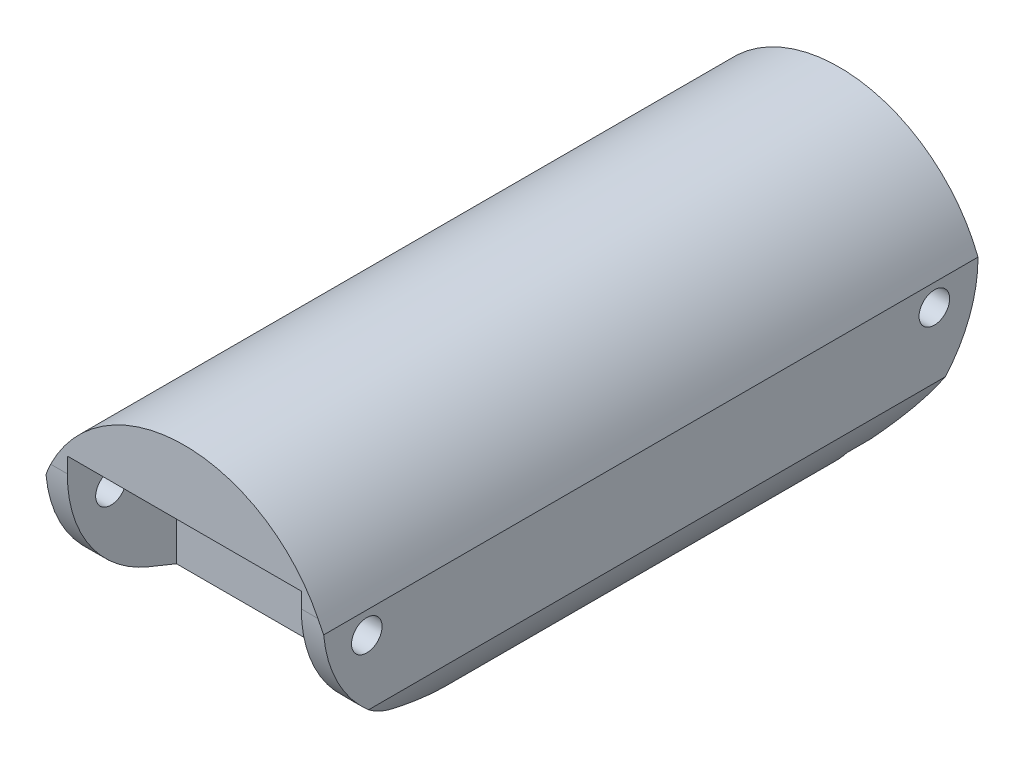
SolidWorks part; units mm, degrees
material "PET"
ref_plane "Front Plane" through (0, 0, 0) normal (0, 0, 1) x (1, 0, 0)
ref_plane "Top Plane" through (0, 0, 0) normal (0, 1, 0) x (1, 0, 0)
ref_plane "Right Plane" through (0, 0, 0) normal (1, 0, 0) x (0, 0, -1)
sketch "Sketch1" plane through (0, 0, 0) normal (0, 0, 1) x (1, 0, 0)
  line L0 (0, 0) -> (0, 5.08)
  line L3 (16.1544, 5.08) -> (16.1544, 0)
  arc A2 (0, 5.08) -> (16.1544, 5.08) centre (8.0772, 1.9574) cw
  arc A3 (0, 0) -> (16.1544, 0) centre (8.0772, 3.1226) ccw
  point P7 (8.0772, -5.5372)
  point P8 (8.0772, 10.6172)
  dimension "D1" = 16.1544
  dimension "D2" = 16.1544
  dimension "D3" = 5.08
extrude "Boss-Extrude1" add sketch "Sketch1" along normal mid plane 38.1 contours A2 L3 A3 L0
sketch "Sketch2" plane through (0, 0, 0) normal (1, 0, 0) x (0, 0, -1)
  line L4 (15.875, 2.54) -> (-49984.125, 2.54) construction
  line L5 (19.05, 5.08) -> (19.05, 0) construction
  line L6 (-19.05, 5.08) -> (-19.05, 0) construction
  line L7 (-19.05, -5.5372) -> (-19.05, 0.635)
  line L8 (-3.81, -5.5372) -> (-19.05, -5.5372)
  line L9 (-19.05, 0.635) -> (-3.81, -5.5372)
  line L10 (0, -1000) -> (0, 49000) construction
  line L18 (19.05, 0.635) -> (19.05, -5.5372)
  line L19 (-16.51, 1.27) -> (-19.05, 1.27)
  line L21 (-16.51, 3.81) -> (-19.05, 3.81)
  line L22 (-19.05, 1.27) -> (-19.05, 3.81)
  line L23 (-15.0884, 2.54) -> (-19.05, 3.81) construction
  line L24 (-15.0884, 2.54) -> (-19.05, 1.27) construction
  line L27 (16.51, 1.27) -> (19.05, 1.27)
  line L28 (19.05, 1.27) -> (19.05, 3.81)
  line L29 (16.51, 3.81) -> (19.05, 3.81)
  line L30 (19.05, -5.5372) -> (8.3594, -5.5372)
  line L31 (-19.05, -5.5372) -> (19.05, -5.5372) construction
  line L32 (8.3594, -5.5372) -> (19.05, 0.635)
  line L33 (-19.05, 10.6172) -> (-19.05, 5.08) construction
  arc A3 (-16.51, 3.81) -> (-16.51, 1.27) centre (-14.3103, 2.54) cw
  arc A4 (16.51, 3.81) -> (16.51, 1.27) centre (14.3103, 2.54) ccw
  point P0 (-15.0884, 2.54)
  point P11 (19.05, 2.54)
  point P14 (-19.05, 2.54)
  point P26 (-19.05, 2.54)
  dimension "D3" = 2.54
  dimension "D4" = 0.635
  dimension "D5" = 60
  dimension "D6" = 0.635
  dimension "D1" = 3.81
extrude "Cut-Extrude1" cut sketch "Sketch2" along normal through all
sketch "Sketch3" plane through (0, 0, 19.05) normal (0, 0, 1) x (1, 0, 0)
  line L3 (-11.7804, 2.54) -> (36.5812, 2.54) construction
  line L4 (8.0772, 9.0576) -> (8.0772, -5.5372) construction
  line L5 (16.1544, 2.54) -> (0, 2.54) construction
  line L6 (16.1544, 2.54) -> (0, 2.54) construction
  line L7 (0, 5.08) -> (0, 0) construction
  line L8 (16.1544, 0.635) -> (0, 0.635) construction
  arc A7 (0, 0) -> (16.1544, 0) centre (8.0772, 3.1226) ccw construction
  arc A9 (14.6124, 0.635) -> (1.542, 0.635) centre (8.0772, 2.54) cw
  arc A13 (5.4577, -3.743) -> (10.6967, -3.743) centre (8.0772, -5.5372) cw
  dimension "D1" = 1.27
  dimension "D2" = 3.175
extrude "Cut-Extrude2" cut sketch "Sketch3" against normal through all contours A13 A9
sketch "Sketch4" plane through (0, 0, 0) normal (-1, 0, 0) x (0, 0, 1)
  line L0 (19.05, 1.27) -> (16.51, 1.27) construction
  line L1 (16.51, 3.81) -> (19.05, 3.81) construction
  line L2 (-16.51, 1.27) -> (-19.05, 1.27) construction
  line L3 (-19.05, 3.81) -> (-16.51, 3.81) construction
  line L4 (19.05, 1.27) -> (16.51, 1.27)
  line L5 (16.51, 3.81) -> (19.05, 3.81)
  line L6 (-16.51, 1.27) -> (-19.05, 1.27)
  line L7 (-19.05, 3.81) -> (-16.51, 3.81)
  line L8 (-19.05, 3.81) -> (-19.05, 1.27)
  line L9 (19.05, 3.81) -> (19.05, 1.27)
  arc A0 (14.3103, 0) -> (16.51, 1.27) centre (14.3103, 2.54) ccw construction
  arc A1 (16.51, 3.81) -> (14.3103, 5.08) centre (14.3103, 2.54) ccw construction
  arc A2 (14.3103, 5.08) -> (14.3103, 0) centre (14.3103, 2.54) ccw construction
  arc A3 (-16.51, 1.27) -> (-14.3103, 0) centre (-14.3103, 2.54) ccw construction
  arc A4 (-14.3103, 5.08) -> (-16.51, 3.81) centre (-14.3103, 2.54) ccw construction
  arc A5 (-14.3103, 0) -> (-14.3103, 5.08) centre (-14.3103, 2.54) ccw construction
  arc A6 (14.3103, 0) -> (16.51, 1.27) centre (14.3103, 2.54) ccw
  arc A7 (16.51, 3.81) -> (14.3103, 5.08) centre (14.3103, 2.54) ccw
  arc A8 (14.3103, 5.08) -> (14.3103, 0) centre (14.3103, 2.54) ccw
  arc A9 (-16.51, 1.27) -> (-14.3103, 0) centre (-14.3103, 2.54) ccw
  arc A10 (-14.3103, 5.08) -> (-16.51, 3.81) centre (-14.3103, 2.54) ccw
  arc A11 (-14.3103, 0) -> (-14.3103, 5.08) centre (-14.3103, 2.54) ccw
extrude "Boss-Extrude2" add sketch "Sketch4" against normal up to surface (16.1544 mm away) up to face at (16.1544, 2.54, 0)
ref_plane "Plane1" through (5.08, 0, 0) normal (-1, 0, 0) x (0, 0, 1)
ref_plane "Plane2" through (8.0772, 0, 0) normal (1, 0, 0) x (0, 0, -1)
sketch "Sketch7" plane through (5.08, 0, 0) normal (-1, 0, 0) x (0, 0, 1)
  line L0 (-19.05, 0) -> (-19.05, 2.8575)
  line L1 (-19.05, 0.635) -> (-19.05, 5.08) construction
  line L2 (-19.05, 2.8575) -> (-16.51, 2.8575)
  line L4 (17.4821, 0) -> (-17.9501, 0) construction
  line L5 (-16.51, 0) -> (-19.05, 0)
  line L6 (-19.05, 2.8575) -> (-19.05, 0) construction
  line L7 (-16.51, 0) -> (-19.05, 0) construction
  line L8 (-16.51, 2.8575) -> (-16.51, 0)
  dimension "D1" = 2.54
extrude "Cut-Extrude3" cut sketch "Sketch7" along normal blind 2.54
sketch "Sketch9" plane through (0, 2.8575, 0) normal (0, -1, 0) x (1, 0, 0)
  line L0 (2.54, -16.51) -> (2.54, -19.05) construction
  line L1 (5.08, -19.05) -> (2.54, -19.05)
  line L2 (5.08, -19.05) -> (5.08, -15.24)
  line L3 (5.08, -15.24) -> (2.54, -15.24)
  line L4 (2.54, -19.05) -> (2.54, -15.24)
  line L5 (5.08, -16.51) -> (5.08, -19.05) construction
  line L6 (2.54, -19.05) -> (5.08, -19.05) construction
  dimension "D1" = 3.81
extrude "Cut-Extrude5" cut sketch "Sketch9" along normal through all
sketch "Sketch11" plane through (0, 2.8575, 0) normal (0, -1, 0) x (1, 0, 0)
  line L4 (5.08, -19.05) -> (5.08, -15.24)
  line L5 (5.08, -15.24) -> (2.54, -15.24)
  line L6 (2.54, -15.24) -> (2.54, -19.05)
  line L7 (2.54, -19.05) -> (5.08, -19.05)
  line L8 (5.08, -19.05) -> (5.08, -15.24)
  line L9 (5.08, -15.24) -> (2.54, -15.24)
  line L10 (2.54, -15.24) -> (2.54, -19.05)
  line L11 (2.54, -19.05) -> (5.08, -19.05)
  dimension "D1" = 0
extrude "Cut-Extrude8" cut sketch "Sketch11" against normal blind 2.54
sketch "Sketch12" plane through (2.54, 0, 0) normal (1, 0, 0) x (0, 0, -1)
  line L4 (15.24, -1.5647) -> (19.05, 0.635)
  line L5 (19.05, 0.635) -> (19.05, 5.3975)
  line L6 (19.05, 5.3975) -> (15.24, 5.3975)
  line L7 (15.24, 5.3975) -> (15.24, -1.5647)
  line L8 (15.24, -1.5647) -> (19.05, 0.635)
  line L10 (19.05, 0.635) -> (19.05, 5.3975)
  line L11 (19.05, 5.3975) -> (15.24, 5.3975)
  line L12 (15.24, 5.3975) -> (15.24, -1.5647)
  dimension "D1" = 0
extrude "Cut-Extrude9" cut sketch "Sketch12" against normal blind 1.27
sketch "Sketch13" plane through (0, 0, -15.24) normal (0, 0, -1) x (-1, 0, 0)
  line L2 (-5.08, 5.3975) -> (-5.08, -0.5842)
  line L3 (-5.08, 0.635) -> (-5.08, -1.5647) construction
  line L4 (-5.08, -1.5647) -> (-1.27, -1.5647)
  line L5 (-1.27, -1.5647) -> (-1.27, 5.3975)
  line L6 (-1.27, 5.3975) -> (-5.08, 5.3975)
  line L7 (-5.08, 5.3975) -> (-5.08, -1.5647)
  line L10 (-1.27, 5.3975) -> (-5.08, 5.3975)
  line L13 (-5.08, -0.5842) -> (-1.27, -0.5842)
  line L14 (-1.27, -1.5647) -> (-1.27, 0.635) construction
  line L15 (-1.27, -0.5842) -> (-1.27, 5.3975)
  line M6 (-1.27, -1.5647) -> (-1.27, 5.3975)
  line M7 (-1.27, 5.3975) -> (-5.08, 5.3975)
  line M12 (-5.08, 5.3975) -> (-5.08, -1.5647)
  dimension "D2" = 0.5842
  dimension "D1" = 0
extrude "Cut-Extrude10" cut sketch "Sketch13" against normal blind 1.27 contours L13 M12 M6 M7
sketch "Sketch14" plane through (0, 5.3975, 0) normal (0, -1, 0) x (1, 0, 0)
  line L2 (16.1544, -19.05) -> (16.1544, -17.9501) construction
  line L4 (1.27, -19.05) -> (5.08, -19.05)
  line L5 (5.08, -19.05) -> (5.08, -13.97)
  line L6 (5.08, -13.97) -> (1.27, -13.97)
  line L7 (1.27, -13.97) -> (1.27, -19.05)
  line L8 (1.27, -19.05) -> (14.8844, -19.05)
  line L9 (14.8844, -19.05) -> (14.8844, -12.7)
  line L10 (14.8844, -12.7) -> (1.27, -12.7)
  line L11 (1.27, -12.7) -> (1.27, -19.05)
  line M5 (1.27, -19.05) -> (5.08, -19.05)
  line M6 (5.08, -19.05) -> (5.08, -13.97)
  line M8 (1.27, -13.97) -> (1.27, -19.05)
  line M13 (5.08, -13.97) -> (1.27, -13.97)
  dimension "D2" = 6.35
  dimension "D3" = 1.27
  dimension "D1" = 0
extrude "Cut-Extrude11" cut sketch "Sketch14" along normal up to next and the other way blind 1.27 contours M8 M5 M6 M13 | L8 L9 L10 L11 region at (3.175, 5.3975, -16.51)
mirror "Mirror3" about plane through (0, 0, 0) normal (0, 0, 1) of "Cut-Extrude9", "Cut-Extrude5", "Cut-Extrude3", "Cut-Extrude8", "Cut-Extrude10", "Cut-Extrude11"
sketch "Sketch10" plane through (0, 0, 0) normal (-1, 0, 0) x (0, 0, 1)
  line L0 (-19.05, 3.81) -> (-19.05, 0) construction
  line L1 (-19.05, 0.635) -> (-19.05, 5.08) construction
  line L2 (-19.05, 0) -> (-16.3757, 0) construction
  line L4 (17.4821, 0) -> (-17.9501, 0) construction
  circle A1 centre (-16.51, 3.81) radius 0.889
  dimension "D1" = 2.54
  dimension "D2" = 1.778
  dimension "D4" = 3.81
extrude "Cut-Extrude7" cut sketch "Sketch10" against normal through all
ref_plane "Plane3" through (0, 0, 0) normal (0, 0, -1) x (-1, 0, 0)
sketch "Sketch16" plane through (0, 0, -12.7) normal (0, 0, -1) x (-1, 0, 0)
  line L0 (-10.7442, 6.3754) -> (-5.4102, 6.3754)
  line L1 (-10.7442, 0.6858) -> (-5.4102, 0.6858)
  line L2 (-10.7442, 0.6858) -> (-10.7442, 6.3754)
  line L4 (-5.4102, 0.6858) -> (-5.4102, 6.3754)
  line L5 (-10.7442, 0.6858) -> (-5.4102, 6.3754) construction
  line L6 (-10.7442, 6.3754) -> (-5.4102, 0.6858) construction
  line L7 (-6.0452, 5.9944) -> (-5.4102, 5.9944) construction
  line L8 (-6.0452, 6.3754) -> (-5.4102, 6.3754)
  line L9 (-6.0452, 5.6134) -> (-5.4102, 5.6134)
  line L10 (-14.7786, -2.3622) -> (-1.3758, -2.3622) construction
  arc A0 (-6.1277, -3.0312) -> (-10.0267, -3.0312) centre (-8.0772, -5.5372) ccw construction
  arc A1 (-6.0452, 6.3754) -> (-6.0452, 5.6134) centre (-6.0452, 5.9944) ccw
  arc A2 (-5.4102, 5.6134) -> (-5.4102, 6.3754) centre (-5.4102, 5.9944) ccw
  arc A3 (-14.8844, -2.2303) -> (-14.1701, -3.0312) centre (-8.0772, 3.1226) ccw construction
  arc A4 (-1.9843, -3.0312) -> (-1.27, -2.2303) centre (-8.0772, 3.1226) ccw construction
  point P0 (-8.0772, 3.5306)
  point P9 (-8.0772, -2.3622)
  point P11 (-5.7277, 5.9944)
  dimension "D1" = 5.6896
  dimension "D2" = 5.334
  dimension "D3" = 0.762
  dimension "D4" = 0.635
  dimension "D5" = 3.048
extrude "Cut-Extrude12" cut sketch "Sketch16" against normal blind 15.875 contours L9 A2 L8 A1
sketch "Sketch20" plane through (0, 0, 12.7) normal (0, 0, 1) x (1, 0, 0)
  line L1 (5.4102, 0.6858) -> (10.7442, 0.6858) construction
  line L2 (5.4102, 0.6858) -> (5.4102, 6.3754) construction
  line L3 (5.4102, 6.3754) -> (10.7442, 6.3754) construction
  line L4 (10.7442, 0.6858) -> (10.7442, 6.3754) construction
  line L5 (5.4102, 0.6858) -> (10.7442, 6.3754) construction
  line L6 (5.4102, 6.3754) -> (10.7442, 0.6858) construction
  line L7 (8.0772, -2.3622) -> (15.7288, -2.3622) construction
  line L8 (10.1092, 5.9944) -> (10.7442, 5.9944) construction
  line L9 (10.1092, 6.3754) -> (10.7442, 6.3754)
  line L10 (10.1092, 5.6134) -> (10.7442, 5.6134)
  arc A2 (10.1092, 6.3754) -> (10.1092, 5.6134) centre (10.1092, 5.9944) ccw
  arc A3 (10.7442, 5.6134) -> (10.7442, 6.3754) centre (10.7442, 5.9944) ccw
  arc A4 (10.6967, -3.743) -> (5.4577, -3.743) centre (8.0772, -5.5372) ccw construction
  point P0 (8.0772, 3.5306)
  point P5 (15.7288, -2.3622)
  point P7 (0, 0)
  point P18 (10.4267, 5.9944)
  dimension "D1" = 3.048
  dimension "D2" = 5.6896
  dimension "D3" = 5.334
  dimension "D4" = 0.635
  dimension "D5" = 0.762
extrude "Cut-Extrude13" cut sketch "Sketch20" against normal blind 15.875
fillet "Fillet1" radius 7.62 4 edges at (15.5194, 0.635, -19.05) (0.635, 0.635, -19.05) (15.5194, 0.635, 19.05) (0.635, 0.635, 19.05)
sketch "Sketch21" plane through (0, 0, 0) normal (-1, 0, 0) x (0, 0, 1)
  text T0 "Mid 2\r\n"
extrude "Cut-Extrude14" cut sketch "Sketch21" against normal blind 1
mirror "Mirror4" about plane through (0, 0, 0) normal (0, 0, -1) of "Cut-Extrude7"
equation "\"D1@Sketch1\"=0.636"
equation "\"D2@Sketch1\"=0.636"
equation "\"D1@Boss-Extrude1\"=1.5"
equation "\"D2@Sketch2\"=0.1"
equation "\"D3@Sketch2\"=0.1"
